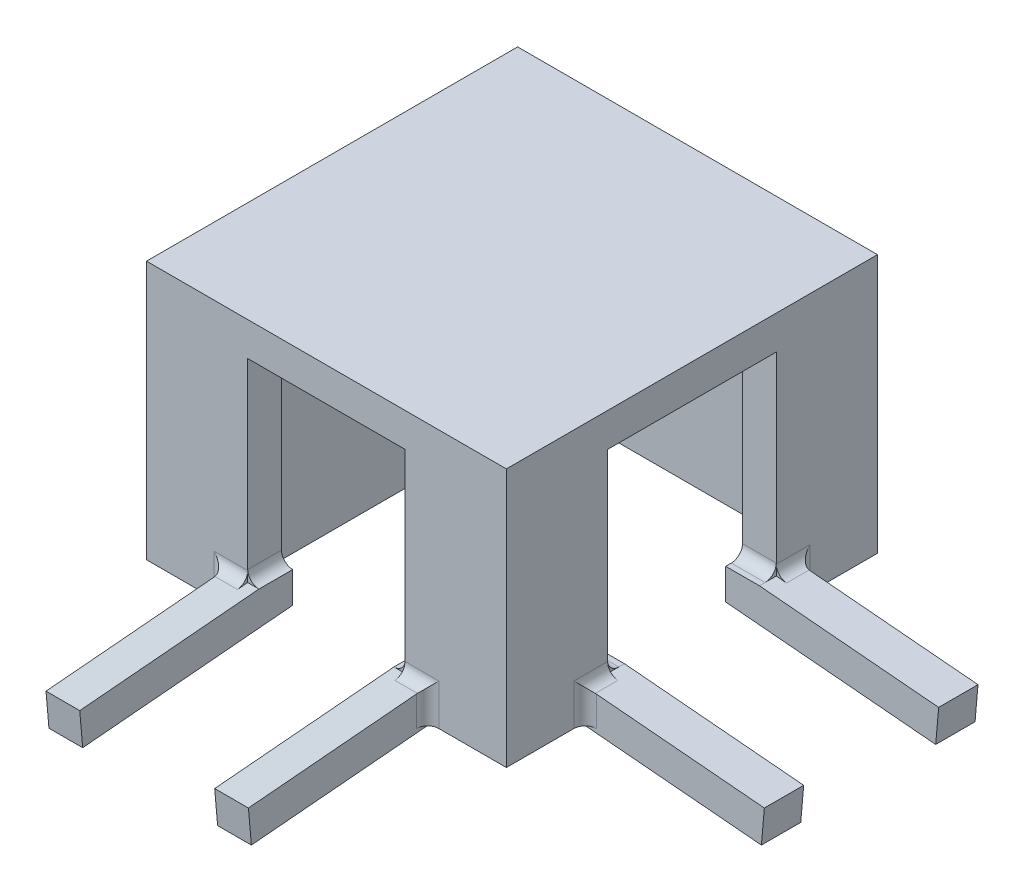
SolidWorks part; units mm, degrees
ref_plane "Front Plane" through (0, 0, 0) normal (0, 0, 1) x (1, 0, 0)
ref_plane "Top Plane" through (0, 0, 0) normal (0, 1, 0) x (1, 0, 0)
ref_plane "Right Plane" through (0, 0, 0) normal (1, 0, 0) x (0, 0, -1)
sketch "Sketch2" plane through (0, 0, 0) normal (0, 1, 0) x (1, 0, 0)
  line L1 (-32, 33) -> (0, 33)
  line L2 (-32, 33) -> (-32, 0)
  line L3 (-32, 0) -> (0, 0)
  line L4 (0, 33) -> (0, 0)
  dimension "D1" = 33
  dimension "D2" = 32
extrude "Boss-Extrude1" add sketch "Sketch2" along normal blind 3
sketch "Sketch3" plane through (0, 0, 0) normal (0, -1, 0) x (1, 0, 0)
  line L1 (-32, 0) -> (0, 0) construction
  line L2 (-26, -30) -> (0, -30) construction
  line L3 (0, 0) -> (0, -33) construction
  line L4 (-26, -24) -> (-23, -24)
  line L5 (0, -33) -> (-32, -33) construction
  line L7 (-32, 0) -> (-32, -33)
  line L8 (-32, -33) -> (0, -33)
  line L9 (0, -33) -> (0, -30)
  line L10 (-32, 0) -> (-23, 0)
  line L11 (-23, 0) -> (-23, -3)
  line L12 (-23, -3) -> (-29, -3)
  line L13 (-29, -3) -> (-29, -6)
  line L14 (-29, -6) -> (-26, -6)
  line L15 (-26, -6) -> (-26, -30) construction
  line L16 (-23, -24) -> (-23, -30)
  line L17 (-26, -6) -> (-26, -24)
  line L18 (-23, -30) -> (0, -30) construction
  line L19 (0, -24) -> (-3, -24)
  line L20 (-3, -24) -> (-3, -30)
  line L21 (-23, -30) -> (-3, -30)
  line L22 (0, -24) -> (0, -30)
  line L23 (-9, 0) -> (-9, -3)
  line L24 (-9, -3) -> (-3, -3)
  line L25 (-3, -3) -> (-3, -6)
  line L26 (-3, -6) -> (-6, -6)
  line L27 (-6, -6) -> (-6, -9)
  line L28 (-6, -9) -> (0, -9)
  line L29 (0, -9) -> (0, 0)
  line L30 (0, 0) -> (-9, 0)
  dimension "D1" = 6
  dimension "D2" = 3
  dimension "D3" = 3
  dimension "D4" = 6
  dimension "D5" = 6
  dimension "D6" = 9
  dimension "D7" = 3
  dimension "D8" = 3
  dimension "D9" = 3
  dimension "D10" = 6
  dimension "D11" = 3
  dimension "D12" = 3
  dimension "D13" = 3
  dimension "D14" = 3
  dimension "D15" = 9
  dimension "D16" = 6
extrude "Boss-Extrude2" add sketch "Sketch3" along normal blind 20
sketch "Sketch6" plane through (-23, 0, 0) normal (1, 0, 0) x (0, 0, -1)
  line L0 (3, -20) -> (-15.6776, -21.6341)
  line L1 (-15.6776, -21.6341) -> (-15.9391, -18.6455)
  line L2 (-15.9391, -18.6455) -> (0, -17.251)
  line L3 (0, -20) -> (0, 0) construction
  line L6 (0, -17.251) -> (3, -17.251)
  line L7 (3, -20) -> (3, 0) construction
  line L8 (3, -17.251) -> (3, -20)
  dimension "D3" = 16
  dimension "D1" = 3
  dimension "D2" = 95
extrude "Boss-Extrude3" add sketch "Sketch6" along normal blind 16 and the other way blind 2
sketch "Sketch8" plane through (0, -17.251, 0) normal (0, 1, 0) x (1, 0, 0)
  line L0 (-9, 3) -> (-23, 3) construction
  line L1 (-22, 3) -> (-10, 3)
  line L2 (-22, 3) -> (-22, -15.9391)
  line L3 (-22, -15.9391) -> (-10, -15.9391)
  line L4 (-10, 3) -> (-10, -15.9391)
  line L5 (-7, -15.9391) -> (-25, -15.9391) construction
  point P8 (-16, 3)
  point P9 (-16, 3)
  point P10 (-16, 3)
  dimension "D1" = 12
extrude "Cut-Extrude1" cut sketch "Sketch8" against normal through all
sketch "Sketch10" plane through (0, 0, -24) normal (0, 0, 1) x (1, 0, 0)
  line L0 (-3, -20) -> (15.6776, -21.6341)
  line L1 (15.6776, -21.6341) -> (15.9391, -18.6455)
  line L2 (15.9391, -18.6455) -> (0, -17.251)
  line L3 (0, -20) -> (0, 0) construction
  line L4 (-3, -20) -> (-3, -17.251)
  line L5 (-3, -20) -> (-3, 0) construction
  line L6 (-3, -17.251) -> (0, -17.251)
  dimension "D1" = 95
  dimension "D2" = 3
  dimension "D3" = 16
extrude "Boss-Extrude4" add sketch "Sketch10" along normal blind 17 and the other way blind 2
sketch "Sketch11" plane through (0, -17.251, 0) normal (0, 1, 0) x (1, 0, 0)
  line L0 (-3, 24) -> (-3, 9) construction
  line L1 (15.9391, 26) -> (15.9391, 7) construction
  line L2 (-3, 10.5) -> (15.9391, 10.5)
  line L3 (-3, 10.5) -> (-3, 22.5)
  line L4 (-3, 22.5) -> (15.9391, 22.5)
  line L5 (15.9391, 10.5) -> (15.9391, 22.5)
  point P0 (-3, 16.5)
  point P7 (-3, 16.5)
  point P8 (0, 0)
  dimension "D1" = 12
extrude "Cut-Extrude2" cut sketch "Sketch11" against normal through all
fillet "Fillet2" radius 1 8 edges at (-25, -18.6255, 0) (-7, -18.6255, 0) (0, -18.6255, -26) (0, -18.6255, -7) (0, -17.251, -25) (0, -17.251, -8) (-24, -17.251, 0) (-8, -17.251, 0)
fillet "Fillet1" radius 1 4 edges at (-9, -17.251, -1.5) (-23, -17.251, -1.5) (-1.5, -17.251, -9) (-1.5, -17.251, -24)
equation "\"rampAngle\"= 95"
equation "\"D1@Sketch10\"=\"rampAngle\""
equation "\"rampLength\" = 16"
equation "\"D3@Sketch10\"=\"rampLength\""
equation "\"D3@Sketch6\"=\"rampLength\""
equation "\"D2@Sketch6\"=\"rampAngle\""
